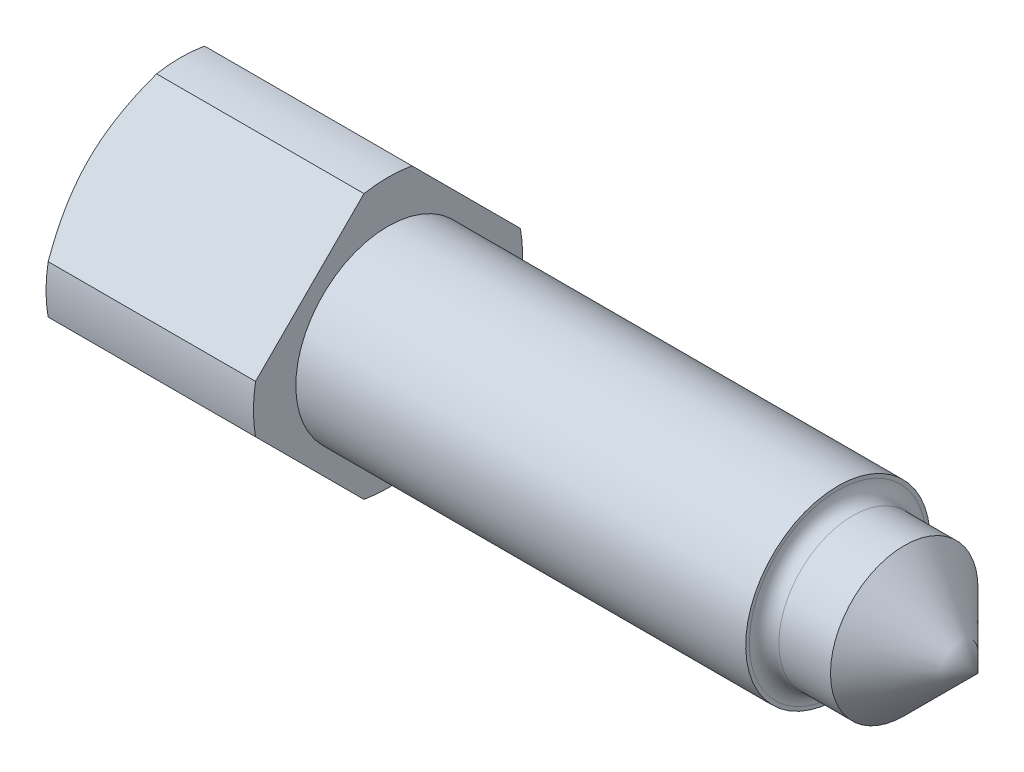
SolidWorks part; units mm, degrees
ref_plane "Front" through (0, 0, 0) normal (0, 0, 1) x (1, 0, 0)
ref_plane "Top" through (0, 0, 0) normal (0, 1, 0) x (1, 0, 0)
ref_plane "Right" through (0, 0, 0) normal (1, 0, 0) x (0, 0, -1)
sketch "Sketch1" plane through (0, 0, 0) normal (1, 0, 0) x (0, 0, -1)
  circle A0 centre (0, 0) radius 3.65
extrude "BaseHead" add sketch "Sketch1" along normal blind 6
sketch "Sketch2" plane through (0, 2.6629, -1.4921) normal (-1, 0, 0) x (0, 0, 1)
  line L1 (5.7347, -2.6629) -> (1.4921, 1.5797)
  line L2 (1.4921, 1.5797) -> (-2.7505, -2.6629)
  line L3 (-2.7505, -2.6629) -> (1.4921, -6.9056)
  line L4 (1.4921, -6.9056) -> (5.7347, -2.6629)
  circle A0 centre (1.4921, -2.6629) radius 3 construction
extrude "Cut-Extrude1" cut sketch "Sketch2" against normal blind 6 flip side to cut
sketch "Sketch3" plane through (1.2597, -5.2747, 0) normal (0, 0, 1) x (0, -1, 0)
  line L0 (-9.2897, -1.2597) -> (-8.2747, -1.2597)
  line L2 (-8.2747, -1.2597) -> (-9.2897, -0.6737)
  line L3 (-9.2897, -0.6737) -> (-9.2897, -1.2597)
  line L4 (-5.2747, 0.2856) -> (-5.2747, -6.82) construction
  line L6 (-5.9259, -1.2597) -> (-8.8662, -1.2597) construction
  dimension "D1" = 8.03
revolve "Cut-Revolve1" cut sketch "Sketch3" angle 360 about L4
sketch "Sketch4" plane through (-10.3472, 12.8472, 0) normal (0, 0, 1) x (0, -1, 0)
  line L0 (12.8472, 16.3472) -> (15.3472, 16.3472)
  line L1 (12.8472, 32.3472) -> (14.8472, 30.3472)
  line L2 (15.3472, 16.3472) -> (15.3472, 28.5472)
  line L3 (12.196, 16.3472) -> (9.2558, 16.3472) construction
  line L4 (14.8472, 28.5472) -> (14.8472, 30.3472)
  line L5 (12.8472, 32.3472) -> (12.8472, 16.3472)
  line L6 (12.8472, 24.434) -> (12.8472, -1.2396) construction
  line L8 (15.3472, 28.5472) -> (14.8472, 28.5472)
  dimension "z" = 3.8
  dimension "D2" = 45
revolve "BaseBody" add sketch "Sketch4" angle 360 about L6
cosmetic thread "ThreadCosmetic1" [suppressed] parameters "D1"=9, "d"=4.5
fillet "Fillet1" radius 0.4 1 edges at (18.2, 2, 0)
fillet "HeadFillet" [suppressed] radius 0.2
sketch "Sketch5" plane through (0, 0, 0) normal (0, 0, 1) x (1, 0, 0)
  line L0 (18.2, 2.2835) -> (18.325, 2.5)
  line L1 (18.325, 2.5) -> (18.325, 2.75)
  line L2 (18.325, 2.75) -> (18.075, 2.75)
  line L3 (18.075, 2.75) -> (18.075, 2.5)
  line L4 (18.075, 2.5) -> (18.2, 2.2835)
  line L5 (0, 0) -> (22.7829, 0) construction
  line L6 (0, 2.1213) -> (0, -2.1213) construction
  line L7 (18.2, -2.5) -> (18.2, 2.5) construction
  dimension "D1" = 5
  dimension "D2" = 0.25
revolve "Cut-Revolve10" [suppressed] cut sketch "Sketch5" angle 360 about L5
pattern_linear "LPattern10" [suppressed] count 30 spacing 0.3 along (-1, 0, 0) of bodies 105
equation "\"D1@Fillet1\" = 2 * \"r@HeadFillet\""
equation "\"d2@Sketch3\" = \"s@Sketch2\""
equation "\"D1@Sketch3\" = \"e@Sketch1\" * 1.1"
equation "\"k+c@BaseHead\" = \"k@Cut-Extrude1\""
equation "\"D1@Sketch5\" = \"d@Sketch4\""
equation "\"D2@Sketch5\" =  ( \"d@Sketch4\" - \"d@ThreadCosmetic1\" )  / 2"
equation "\"D3@LPattern10\" = \"D2@Sketch5\" * 1.2"
equation "\"D1@LPattern10\" = \"D1@ThreadCosmetic1\" / \"D3@LPattern10\""
